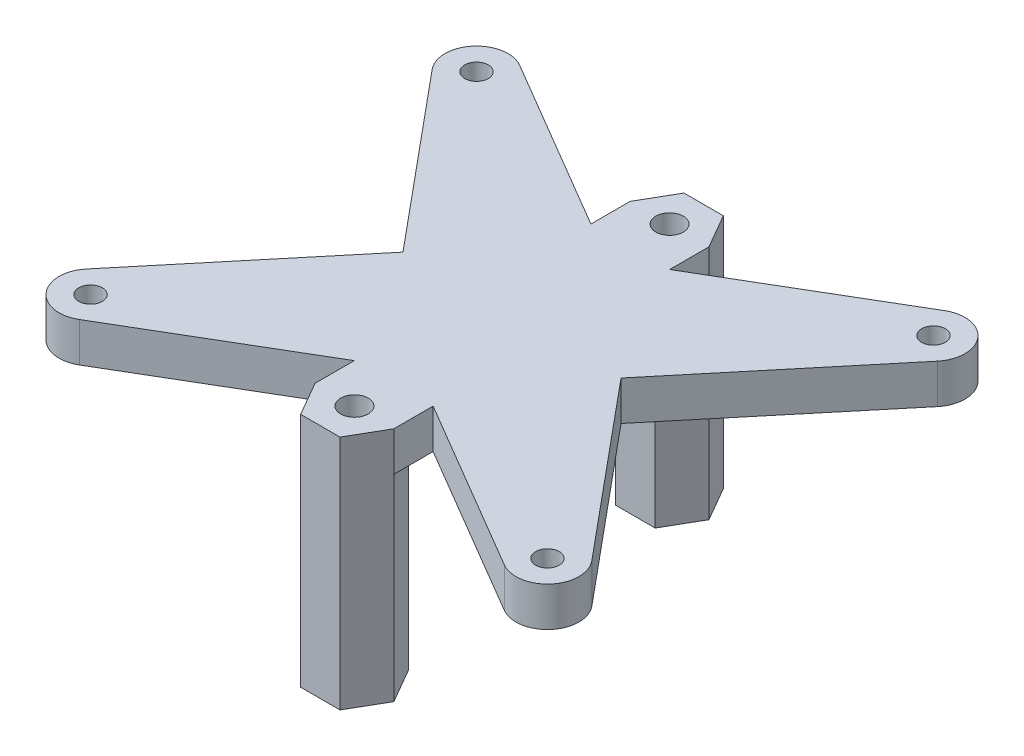
SolidWorks part; units mm, degrees
ref_plane "Plan de face" through (0, 0, 0) normal (0, 0, 1) x (1, 0, 0)
ref_plane "Plan de dessus" through (0, 0, 0) normal (0, 1, 0) x (1, 0, 0)
ref_plane "Plan de droite" through (0, 0, 0) normal (1, 0, 0) x (0, 0, -1)
sketch "Esquisse1" plane through (0, 0, 0) normal (0, 1, 0) x (1, 0, 0)
  line L0 (-32.0764, 21.9435) -> (-13.841, 0)
  line L7 (-13.841, 0) -> (-32.0764, -21.9435)
  line L8 (-26.9711, 27.9472) -> (0, 12.073)
  line L9 (0, 12.073) -> (26.9711, 27.9472)
  line L12 (-32.0764, -21.9435) -> (-13.841, 0)
  line L13 (0, -12.073) -> (26.9711, -27.9472)
  line L14 (-26.9711, -27.9472) -> (0, -12.073)
  line L15 (13.841, 0) -> (32.0764, -21.9435)
  line L16 (32.0764, 21.9435) -> (13.841, 0)
  arc A4 (-26.9711, 27.9472) -> (-32.0764, 21.9435) centre (-29, 24.5) ccw
  arc A7 (32.0764, 21.9435) -> (26.9711, 27.9472) centre (29, 24.5) ccw
  arc A8 (26.9711, -27.9472) -> (32.0764, -21.9435) centre (29, -24.5) ccw
  arc A9 (-32.0764, -21.9435) -> (-26.9711, -27.9472) centre (-29, -24.5) ccw
  point P0 (0, 0)
  point P17 (0, 12.073)
  point P20 (0, 0)
  point P21 (-13.841, 0)
  dimension "D7" = 8
  dimension "D1" = 58
  dimension "D2" = 49
extrude "Boss.-Extru.1" add sketch "Esquisse1" along normal blind 5 contours L7 A9 L14 L13 A8 L15 L16 A7 L9 L8 A4 L0 region at (0, 0, 0)
sketch "Esquisse2" plane through (0, 5, 0) normal (0, 1, 0) x (1, 0, 0)
  circle A0 centre (-29, 24.5) radius 4
  circle A1 centre (29, 24.5) radius 4
  circle A2 centre (-29, -24.5) radius 4
  circle A3 centre (29, -24.5) radius 4
  circle A4 centre (-29, 24.5) radius 1.5
  circle A5 centre (29, 24.5) radius 1.5
  circle A6 centre (29, -24.5) radius 1.5
  circle A7 centre (-29, -24.5) radius 1.5
  dimension "D1" = 3
  dimension "D2" = 3
  dimension "D3" = 3
  dimension "D4" = 3
extrude "Enlèv. mat.-Extru.2" cut sketch "Esquisse2" against normal blind 5 contours A4 | A7 | A6 | A5
sketch "Esquisse4" plane through (0, 0, 0) normal (0, -1, 0) x (1, 0, 0)
  line L0 (0, 20) -> (0, -20) construction
  line L1 (-5, 20) -> (-5, 15.0158)
  line L2 (5, 20) -> (2.5, 24.3301)
  line L3 (2.5, 24.3301) -> (-2.5, 24.3301)
  line L4 (-2.5, 24.3301) -> (-5, 20)
  line L5 (-5, 20) -> (-2.5, 15.6699)
  line L6 (-2.5, 15.6699) -> (2.5, 15.6699)
  line L7 (2.5, 15.6699) -> (5, 20)
  line L8 (5, -20) -> (2.5, -15.6699)
  line L9 (2.5, -15.6699) -> (-2.5, -15.6699)
  line L10 (-2.5, -15.6699) -> (-5, -20)
  line L11 (-5, -20) -> (-2.5, -24.3301)
  line L12 (-2.5, -24.3301) -> (2.5, -24.3301)
  line L13 (2.5, -24.3301) -> (5, -20)
  line L14 (-26.9711, 27.9472) -> (0, 12.073) construction
  line L15 (5, 20) -> (5, 15.0158)
  line L16 (0, 12.073) -> (26.9711, 27.9472) construction
  line L17 (-5, -20) -> (-5, -15.0158)
  line L18 (-26.9711, -27.9472) -> (0, -12.073) construction
  line L19 (5, -20) -> (5, -15.0158)
  line L20 (0, -12.073) -> (26.9711, -27.9472) construction
  line L21 (-5, 15.0158) -> (0, 12.073)
  line L22 (0, 12.073) -> (5, 15.0158)
  line L23 (-5, -15.0158) -> (0, -12.073)
  line L24 (0, -12.073) -> (5, -15.0158)
  circle A0 centre (0, 20) radius 1.75
  circle A1 centre (0, -20) radius 1.75
  circle A2 centre (0, 20) radius 4.3301 construction
  circle A3 centre (0, -20) radius 4.3301 construction
  line M15 (-26.9711, -27.9472) -> (0, -12.073)
  line M16 (0, -12.073) -> (26.9711, -27.9472)
  line M21 (26.9711, 27.9472) -> (0, 12.073)
  line M22 (0, 12.073) -> (-26.9711, 27.9472)
  dimension "D2" = 3.5
  dimension "D3" = 3.5
  dimension "D1" = 40
  dimension "D4" = 10
  dimension "D5" = 10
extrude "Boss.-Extru.6" add sketch "Esquisse4" against normal blind 5 contours L8 L19 L17 L10 L9 M16 M15 | L12 L13 L8 L9 L10 L11 A1 | L15 L7 L6 L5 L1 M22 M21 | L6 L7 L2 L3 L4 L5 A0 region at (0, 0, 15.3404) region at (-3.6354, 0, 22.0989) region at (3.6354, 0, -22.0989) region at (0, 0, -15.3404)
extrude "Boss.-Extru.7" add sketch "Esquisse4<3>" along normal blind 14.5 contours L6 L7 L2 L3 L4 L5 A0 | L12 L13 L8 L9 L10 L11 A1 region at (-3.6354, 0, 22.0989) region at (3.6354, 0, -22.0989)
sketch "Esquisse4<3>" plane through (0, 0, 0) normal (0, -1, 0) x (1, 0, 0) same geometry as "Esquisse4"
sketch "Esquisse5" plane through (0, -14.5, 0) normal (0, -1, 0) x (1, 0, 0)
  line L1 (2.8868, 20) -> (1.4434, 22.5)
  line L2 (1.4434, 22.5) -> (-1.4434, 22.5)
  line L3 (-1.4434, 22.5) -> (-2.8868, 20)
  line L4 (-2.8868, 20) -> (-1.4434, 17.5)
  line L5 (-1.4434, 17.5) -> (1.4434, 17.5)
  line L6 (1.4434, 17.5) -> (2.8868, 20)
  line L7 (5, 20) -> (2.5, 24.3301)
  line L8 (2.5, 24.3301) -> (-2.5, 24.3301)
  line L9 (-2.5, 24.3301) -> (-5, 20)
  line L10 (-5, 20) -> (-2.5, 15.6699)
  line L11 (-2.5, 15.6699) -> (2.5, 15.6699)
  line L12 (2.5, 15.6699) -> (5, 20)
  line L13 (5, -20) -> (2.5, -15.6699)
  line L14 (2.5, -15.6699) -> (-2.5, -15.6699)
  line L15 (-2.5, -15.6699) -> (-5, -20)
  line L16 (-5, -20) -> (-2.5, -24.3301)
  line L17 (-2.5, -24.3301) -> (2.5, -24.3301)
  line L18 (2.5, -24.3301) -> (5, -20)
  line L19 (3.1754, -20) -> (1.5877, -17.25)
  line L20 (1.5877, -17.25) -> (-1.5877, -17.25)
  line L21 (-1.5877, -17.25) -> (-3.1754, -20)
  line L22 (-3.1754, -20) -> (-1.5877, -22.75)
  line L23 (-1.5877, -22.75) -> (1.5877, -22.75)
  line L24 (1.5877, -22.75) -> (3.1754, -20)
  circle A0 centre (0, 20) radius 2.5 construction
  circle A1 centre (0, 20) radius 4.3301 construction
  circle A2 centre (0, -20) radius 4.3301 construction
  circle A3 centre (0, -20) radius 2.75 construction
  dimension "D1" = 5
  dimension "D2" = 5.5
extrude "Boss.-Extru.8" add sketch "Esquisse5" along normal blind 2.5
extrude "Boss.-Extru.10" add sketch "Esquisse4<6>" along normal blind 8 from offset 17 contours L6 L7 L2 L3 L4 L5 A0 | L12 L13 L8 L9 L10 L11 A1 region at (-3.6354, 0, 22.0989) region at (3.6354, 0, -22.0989)
sketch "Esquisse4<6>" plane through (0, 0, 0) normal (0, -1, 0) x (1, 0, 0) same geometry as "Esquisse4"
